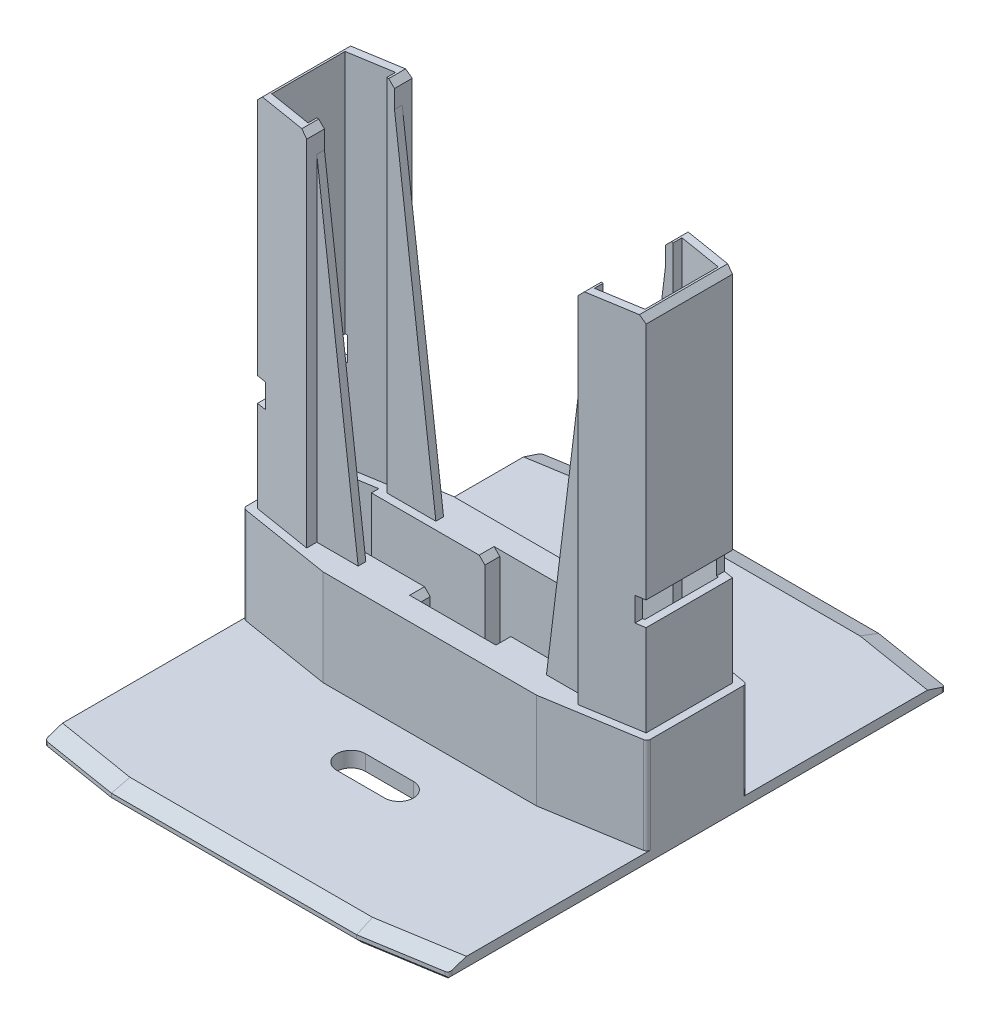
SolidWorks part; units mm, degrees
ref_plane "Front" through (0, 0, 0) normal (0, 0, 1) x (1, 0, 0)
ref_plane "Top" through (0, 0, 0) normal (0, 1, 0) x (1, 0, 0)
ref_plane "Right" through (0, 0, 0) normal (1, 0, 0) x (0, 0, -1)
sketch "Sketch1" plane through (0, 0, 0) normal (0, 1, 0) x (1, 0, 0)
  line L0 (0, -738.6263) -> (0, 36192.6906) construction
  line L1 (-738.6263, 0) -> (36192.6906, 0) construction
  line L2 (-40.5, -9) -> (-40.5, 9)
  line L3 (-40.5, 9) -> (-28.25, 11)
  line L4 (-28.25, 11) -> (-28.25, 8.9)
  line L5 (-28.25, 8.9) -> (-11, 8.9)
  line L6 (-11, 8.9) -> (-11, 12)
  line L7 (-11, 12) -> (11, 12)
  line L8 (-11, -12) -> (11, -12)
  line L9 (-11, -8.9) -> (-11, -12)
  line L10 (-28.25, -8.9) -> (-11, -8.9)
  line L11 (-28.25, -11) -> (-28.25, -8.9)
  line L12 (-40.5, -9) -> (-28.25, -11)
  line L13 (40.5, -9) -> (28.25, -11)
  line L14 (28.25, -11) -> (28.25, -8.9)
  line L15 (28.25, -8.9) -> (11, -8.9)
  line L16 (11, -8.9) -> (11, -12)
  line L17 (11, 8.9) -> (11, 12)
  line L18 (28.25, 8.9) -> (11, 8.9)
  line L19 (28.25, 11) -> (28.25, 8.9)
  line L20 (40.5, 9) -> (28.25, 11)
  line L21 (40.5, -9) -> (40.5, 9)
  line L42 (-22.2548, 13.6) -> (22.2548, 13.6)
  line L43 (-42.1, -10.36) -> (-42.1, 10.36)
  line L44 (-42.1, 10.36) -> (-22.2548, 13.6)
  line L45 (42.1, 10.36) -> (22.2548, 13.6)
  line L46 (42.1, -10.36) -> (42.1, 10.36)
  line L47 (42.1, -10.36) -> (22.2548, -13.6)
  line L48 (-22.2548, -13.6) -> (22.2548, -13.6)
  line L49 (-42.1, -10.36) -> (-22.2548, -13.6)
  line L50 (-1066.7659, 42.5) -> (48933.2341, 42.5) construction
  line L51 (-1082.2929, -42.5) -> (48917.7071, -42.5) construction
  line L52 (-38.9, 7.64) -> (-29.85, 9.1176)
  line L53 (-29.85, 9.1176) -> (-29.85, 7.3)
  line L54 (-29.85, 7.3) -> (-9.4, 7.3)
  line L55 (-9.4, 7.3) -> (-9.4, 10.4)
  line L56 (-9.4, 10.4) -> (9.4, 10.4)
  line L57 (9.4, 7.3) -> (9.4, 10.4)
  line L58 (29.85, 7.3) -> (9.4, 7.3)
  line L59 (29.85, 9.1176) -> (29.85, 7.3)
  line L60 (38.9, 7.64) -> (29.85, 9.1176)
  line L61 (38.9, -7.64) -> (38.9, 7.64)
  line L62 (38.9, -7.64) -> (29.85, -9.1176)
  line L63 (29.85, -9.1176) -> (29.85, -7.3)
  line L64 (29.85, -7.3) -> (9.4, -7.3)
  line L65 (9.4, -7.3) -> (9.4, -10.4)
  line L66 (-9.4, -10.4) -> (9.4, -10.4)
  line L67 (-9.4, -7.3) -> (-9.4, -10.4)
  line L68 (-29.85, -7.3) -> (-9.4, -7.3)
  line L69 (-29.85, -9.1176) -> (-29.85, -7.3)
  line L70 (-38.9, -7.64) -> (-29.85, -9.1176)
  line L71 (-38.9, -7.64) -> (-38.9, 7.64)
  line L72 (-31.45, -5.7) -> (-7.8, -5.7)
  line L73 (-7.8, -5.7) -> (-7.8, -8.8)
  line L74 (-7.8, -8.8) -> (7.8, -8.8)
  line L75 (7.8, -5.7) -> (7.8, -8.8)
  line L76 (31.45, -5.7) -> (7.8, -5.7)
  line L77 (31.45, -7.2352) -> (31.45, -5.7)
  line L78 (37.3, -6.2801) -> (31.45, -7.2352)
  line L79 (37.3, -6.2801) -> (37.3, 6.2801)
  line L80 (37.3, 6.2801) -> (31.45, 7.2352)
  line L81 (31.45, 7.2352) -> (31.45, 5.7)
  line L82 (31.45, 5.7) -> (7.8, 5.7)
  line L83 (7.8, 5.7) -> (7.8, 8.8)
  line L84 (-7.8, 8.8) -> (7.8, 8.8)
  line L85 (-7.8, 5.7) -> (-7.8, 8.8)
  line L86 (-31.45, 5.7) -> (-7.8, 5.7)
  line L87 (-31.45, 7.2352) -> (-31.45, 5.7)
  line L88 (-37.3, 6.2801) -> (-31.45, 7.2352)
  line L89 (-37.3, -6.2801) -> (-37.3, 6.2801)
  line L90 (-37.3, -6.2801) -> (-31.45, -7.2352)
  line L91 (-31.45, -7.2352) -> (-31.45, -5.7)
  point P17 (-40.5, 0)
  point P22 (0, -12)
  point P23 (0, 12)
  point P27 (40.5, 0)
  point P54 (0, 13.6)
  point P57 (42.1, 0)
  point P60 (-42.1, 0)
  dimension "D1" = 81
  dimension "D2" = 24
  dimension "D4" = 18
  dimension "D5" = 17.25
  dimension "D6" = 12.25
  dimension "D7" = 3.1
  dimension "D9" = 85
  dimension "D10" = 42.5
  dimension "D11" = 1.6
  dimension "D12" = 1.6
  dimension "D13" = 1.6
  dimension "D3" = 22
  dimension "D8" = 1.6
  dimension "D15" = 1.6
extrude "Boss-Extrude1" add sketch "Sketch1" along normal blind 23.2 contours L49 L48 L47 L46 L45 L42 L44 L43
extrude "Boss-Extrude2" add sketch "Sketch1<3>" along normal blind 75 from surface contours L13 L21 L20 L19 L18 L17 L7 L6 L5 L4 L3 L2 L12 L11 L10 L9 L8 L16 L15 L14 L70 L71 L52 L53 L54 L55 L56 L57 L58 L59 L60 L61 L62 L63 L64 L65 L66 L67 L68 L69 region at (-39.6552, 0, 0) starting at face at (0, 23.2, 0)
sketch "Sketch1<3>" plane through (0, 0, 0) normal (0, 1, 0) x (1, 0, 0) same geometry as "Sketch1"
sketch "Sketch2" plane through (0, 0, 0) normal (0, 0, 1) x (1, 0, 0)
  line L0 (0, -1007.7521) -> (0, 48992.2479) construction
  line L2 (-40.5, 47.2) -> (-38.5, 47.2)
  line L3 (-40.5, 47.2) -> (-40.5, 42.2)
  line L4 (-40.5, 42.2) -> (-38.5, 42.2)
  line L5 (-38.5, 47.2) -> (-38.5, 42.2)
  line L6 (-40.5, 47.2) -> (-38.5, 42.2) construction
  line L7 (-40.5, 42.2) -> (-38.5, 47.2) construction
  line L8 (-40.5, 98.2) -> (-40.5, 23.2) construction
  line L9 (40.5, 42.2) -> (38.5, 47.2) construction
  line L10 (40.5, 47.2) -> (38.5, 42.2) construction
  line L11 (38.5, 47.2) -> (38.5, 42.2)
  line L12 (40.5, 42.2) -> (38.5, 42.2)
  line L13 (40.5, 47.2) -> (40.5, 42.2)
  line L14 (40.5, 47.2) -> (38.5, 47.2)
  line L16 (-40.5, 98.2) -> (-28.25, 98.2) construction
  point P1 (-39.5, 44.7)
  point P16 (39.5, 44.7)
  dimension "D1" = 2
  dimension "D2" = 5
  dimension "D3" = 51
extrude "Cut-Extrude1" cut sketch "Sketch2" against normal through all both and the other way through all
sketch "Sketch3" plane through (0, 0, 0) normal (0, 0, 1) x (1, 0, 0)
  line L0 (0, -1021.8671) -> (0, 48978.1329) construction
  line L2 (-11, 98.2) -> (11, 98.2) construction
  line L3 (-28.25, 93.2) -> (-19.625, 23.2)
  line L4 (-19.625, 23.2) -> (19.625, 23.2)
  line L5 (28.25, 93.2) -> (19.625, 23.2)
  line L6 (-19.625, -996.8) -> (-19.625, 49003.2) construction
  line L7 (-28.25, 23.2) -> (-11, 23.2) construction
  line L8 (19.625, -996.8) -> (19.625, 49003.2) construction
  line L9 (28.25, 23.2) -> (11, 23.2) construction
  line L10 (-42.1, 23.2) -> (-22.2548, 23.2) construction
  line L13 (-28.25, 98.2) -> (-28.25, 23.2) construction
  line L14 (-28.25, 93.2) -> (-28.25, 98.2)
  line L15 (-28.25, 98.2) -> (28.25, 98.2)
  line L16 (28.25, 98.2) -> (28.25, 93.2)
  point P12 (0, 3.2)
  point P13 (0, 98.2)
  point P18 (-19.625, 23.2)
  point P23 (19.625, 23.2)
  dimension "D1" = 5
extrude "Cut-Extrude2" cut sketch "Sketch3" against normal through all both and the other way through all
sketch "Sketch4" plane through (0, 0, 0) normal (0, 1, 0) x (1, 0, 0)
  line L9 (0, -1000) -> (0, 49000) construction
  line L12 (-1000, 0) -> (49000, 0) construction
  line L39 (23.2928, 26.4) -> (44.1625, 22.9927)
  line L40 (-23.2928, 26.4) -> (23.2928, 26.4)
  line L41 (-44.1625, 22.9927) -> (-23.2928, 26.4)
  line L42 (23.2928, 26.4) -> (42.1, 23.3294)
  line L43 (-23.2928, 26.4) -> (23.2928, 26.4)
  line L44 (-42.1, 23.3294) -> (-23.2928, 26.4)
  line L45 (-42.1, -10.36) -> (-42.1, 10.36) construction
  line L46 (42.1, -10.36) -> (42.1, 10.36) construction
  line L47 (-42.1, -23.3294) -> (-42.1, 23.3294)
  line L48 (23.2928, -26.4) -> (44.1625, -22.9927)
  line L49 (-23.2928, -26.4) -> (23.2928, -26.4)
  line L50 (-44.1625, -22.9927) -> (-23.2928, -26.4)
  line L51 (23.2928, -26.4) -> (42.1, -23.3294)
  line L52 (-23.2928, -26.4) -> (23.2928, -26.4)
  line L53 (-42.1, -23.3294) -> (-23.2928, -26.4)
  line L54 (42.1, -23.3294) -> (42.1, 23.3294)
  dimension "D1" = 12.8
  dimension "D2" = 12.8
extrude "Boss-Extrude3" add sketch "Sketch4" along normal blind 3.2
extrude "Cut-Extrude3" cut sketch "Sketch1<4>" against normal through all and the other way through all contours L90 L91 L72 L73 L74 L75 L76 L77 L78 L79 L80 L81 L82 L83 L84 L85 L86 L87 L88 L89
sketch "Sketch1<4>" plane through (0, 0, 0) normal (0, 1, 0) x (1, 0, 0) same geometry as "Sketch1"
sketch "Sketch5" plane through (0, 0, 0) normal (0, 1, 0) x (1, 0, 0)
  line L6 (0, -1000) -> (0, 49000) construction
  line L16 (-1000, 0) -> (49000, 0) construction
  line L17 (-986.3057, 42.5) -> (49013.6943, 42.5) construction
  line L18 (-977.9486, -42.5) -> (49022.0514, -42.5) construction
  line L21 (42.1, 23.3294) -> (23.2928, 26.4) construction
  line L22 (23.2928, 26.4) -> (-23.2928, 26.4) construction
  line L23 (-23.2928, 26.4) -> (-42.1, 23.3294) construction
  line L24 (42.1, 23.3294) -> (23.2928, 26.4)
  line L25 (23.2928, 26.4) -> (-23.2928, 26.4)
  line L26 (-23.2928, 26.4) -> (-42.1, 23.3294)
  line L28 (23.2928, -26.4) -> (42.1, -23.3294) construction
  line L31 (-23.2928, -26.4) -> (23.2928, -26.4) construction
  line L41 (-42.1, -51.7002) -> (-25.5635, -54.4)
  line L42 (-25.5635, -54.4) -> (25.5635, -54.4)
  line L43 (25.5635, -54.4) -> (42.1, -51.7002)
  line L44 (-42.1, -23.3294) -> (-42.1, -51.7002)
  line L45 (42.1, -23.3294) -> (42.1, -51.7002)
  line L46 (-42.1, 23.3294) -> (-42.1, 51.7002)
  line L47 (-42.1, -23.3294) -> (-23.2928, -26.4) construction
  line L48 (23.2928, -26.4) -> (42.1, -23.3294)
  line L49 (42.1, 23.3294) -> (42.1, 51.7002)
  line L62 (25.5635, 54.4) -> (42.1, 51.7002)
  line L63 (-25.5635, 54.4) -> (25.5635, 54.4)
  line L64 (-42.1, 51.7002) -> (-25.5635, 54.4)
  line L65 (-23.2928, -26.4) -> (23.2928, -26.4)
  line L66 (-42.1, -23.3294) -> (-23.2928, -26.4)
  point P5 (-45.5781, -51.0515)
  point P9 (45.5781, -51.0515)
  dimension "D1" = 85
  dimension "D2" = 42.5
  dimension "D3" = 28
  dimension "D4" = 28
  dimension "D5" = 28
extrude "Boss-Extrude4" add sketch "Sketch5" along normal up to surface (3.2 mm away) up to face at (0, 3.2, 18.4223)
sketch "Sketch6" plane through (0, 0, 0) normal (0, 1, 0) x (1, 0, 0)
  line L4 (0, 0) -> (50000, 0) construction
  line L7 (25.5635, 54.4) -> (42.1, 51.7002) construction
  line L8 (-25.5635, 54.4) -> (25.5635, 54.4) construction
  line L24 (-42.1, 51.7002) -> (-25.5635, 54.4) construction
  line L25 (25.5635, 54.4) -> (42.1, 51.7002)
  line L26 (-25.5635, 54.4) -> (25.5635, 54.4)
  line L27 (-42.1, 51.7002) -> (-25.5635, 54.4)
  line L30 (-42.1, -10.36) -> (-42.1, 10.36) construction
  line L31 (42.1, -10.36) -> (42.1, 10.36) construction
  line L32 (-42.1, 48.1002) -> (42.1, 48.1002)
  line L33 (-42.1, 48.1002) -> (-42.1, 51.7002)
  line L34 (42.1, 48.1002) -> (42.1, 51.7002)
  line L35 (42.1, -48.1002) -> (42.1, -51.7002)
  line L36 (-42.1, -48.1002) -> (-42.1, -51.7002)
  line L37 (-42.1, -48.1002) -> (42.1, -48.1002)
  line L38 (-42.1, -51.7002) -> (-25.5635, -54.4)
  line L39 (-25.5635, -54.4) -> (25.5635, -54.4)
  line L40 (25.5635, -54.4) -> (42.1, -51.7002)
  point P2 (-42.1, 40.9)
  point P3 (42.1, 40.9)
  dimension "D1" = 3.6
extrude "Boss-Extrude5" add sketch "Sketch6" along normal up to surface (3.2 mm away) up to face at (0, 3.2, 32.515)
sketch "Sketch7" plane through (0, 0, 0) normal (0, 1, 0) x (0, 0, -1)
  line L0 (25, -5) -> (25, 5) construction
  line L5 (28, -5) -> (28, 5)
  line L6 (22, -5) -> (22, 5)
  line L8 (0, -1000) -> (0, 49000) construction
  line L17 (-25, -5) -> (-25, 5) construction
  line L22 (-28, -5) -> (-28, 5)
  line L23 (-22, -5) -> (-22, 5)
  arc A2 (-28, -5) -> (-22, -5) centre (-25, -5) ccw
  arc A3 (-22, 5) -> (-28, 5) centre (-25, 5) ccw
  arc A4 (28, -5) -> (22, -5) centre (25, -5) cw
  arc A5 (22, 5) -> (28, 5) centre (25, 5) cw
  point P4 (-25, 0)
  point P15 (25, 0)
  dimension "D1" = 25
  dimension "D2" = 3
  dimension "D3" = 10
extrude "Cut-Extrude4" cut sketch "Sketch7" against normal up to surface (-23.2 mm away) contours L5 | L23 A3 L22 A2 | A5 L6 A4 L5 region at (0, 0, -25) region at (0, 0, 25) up to face at (0, 23.2, 0)
chamfer "Chamfer1" distance 1.2 distance2 3.6 6 edges at (33.8317, 3.2, 53.0501) (-33.8317, 3.2, 53.0501) (0, 3.2, 54.4) (-33.8317, 3.2, -53.0501) (0, 3.2, -54.4) (33.8317, 3.2, -53.0501) tangent propagation no first distance on face at (33.8317, 1.6, 53.0501) first distance on face at (-33.8317, 1.6, 53.0501) first distance on face at (0, 1.6, 54.4) first distance on face at (-33.8317, 1.6, -53.0501) first distance on face at (0, 1.6, -54.4) first distance on face at (33.8317, 1.6, -53.0501)
chamfer "Chamfer2" distance 1.2 angle 45 22 edges at (33.8317, 0, 53.0501) (0, 0, 54.4) (-33.8317, 0, 53.0501) (-42.1, 0, 0) (-33.8317, 0, -53.0501) (0, 0, -54.4) (33.8317, 0, -53.0501) (42.1, 0, 0) (40.5, 98.2, 0) (-40.5, 98.2, 0) (28.25, 98.2, -9.15) (28.25, 98.2, 9.15) (-28.25, 98.2, -9.15) (-28.25, 98.2, 9.15) (-7.8, 0, 7.25) (-7.8, 0, -7.25) (7.8, 0, 7.25) (7.8, 0, -7.25) (7.8, 23.2, 7.25) (7.8, 23.2, -7.25) (-7.8, 23.2, -7.25) (-7.8, 23.2, 7.25)
fillet "Fillet1" radius 0.8 8 edges at (42.1, 1.6, 51.7002) (42.1, 1.6, -51.7002) (-42.1, 1.6, -51.7002) (-42.1, 1.6, 51.7002) (42.1, 13.2, -10.36) (42.1, 13.2, 10.36) (-42.1, 13.2, 10.36) (-42.1, 13.2, -10.36)
equation "\"D11@Sketch1\"=\"D8@Sketch1\""
equation "\"D12@Sketch1\"=\"D8@Sketch1\""
equation "\"D13@Sketch1\"=\"D8@Sketch1\""
equation "\"D2@Sketch5\"=\"D1@Sketch5\"/2"
